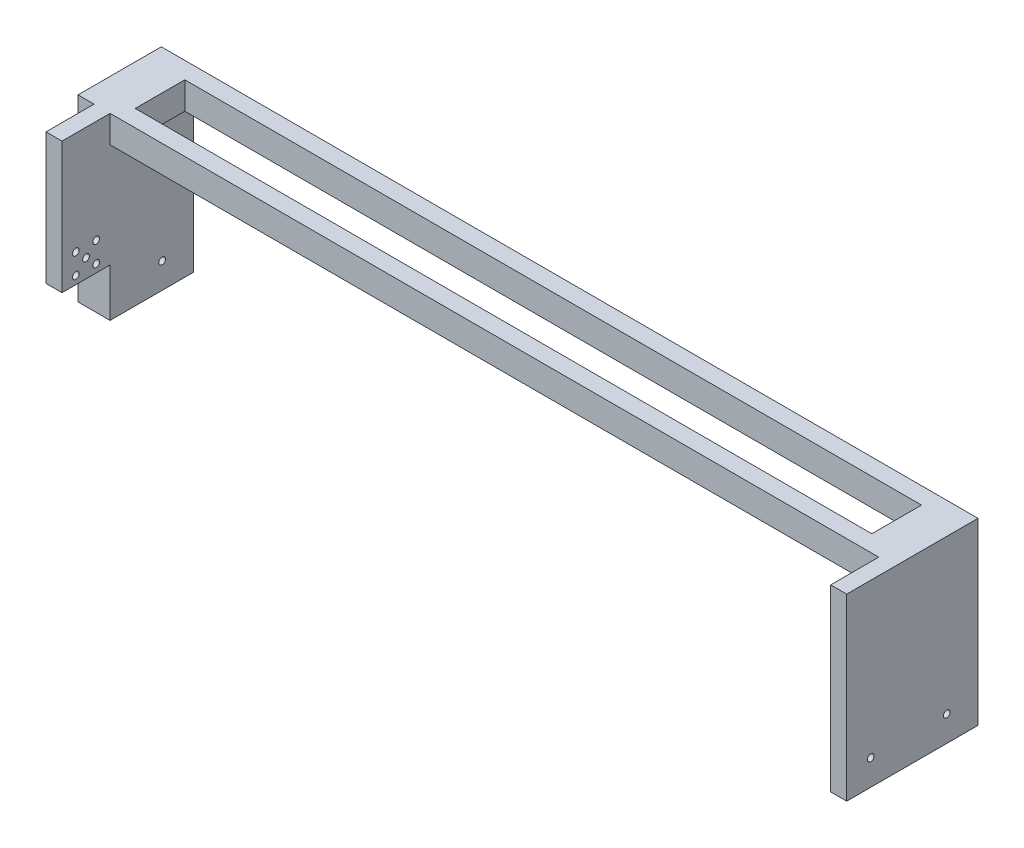
SolidWorks part; units mm, degrees
ref_plane "Front Plane" through (0, 0, 0) normal (0, 0, 1) x (1, 0, 0)
ref_plane "Top Plane" through (0, 0, 0) normal (0, 1, 0) x (1, 0, 0)
ref_plane "Right Plane" through (0, 0, 0) normal (1, 0, 0) x (0, 0, -1)
sketch "Sketch1" plane through (0, 0, 0) normal (0, 1, 0) x (1, 0, 0)
  line L0 (10, -82) -> (10, -52)
  line L1 (10, -52) -> (0, -52)
  line L2 (0, -52) -> (0, 0)
  line L4 (0, 0) -> (510, 0)
  line L5 (510, 0) -> (510, -82)
  line L8 (510, -82) -> (500, -82)
  line L9 (20, -82) -> (20, -52)
  line L10 (20, -52) -> (500, -52)
  line L11 (500, -52) -> (500, -82)
  line L12 (20, -82) -> (10, -82)
  dimension "D1" = 480
  dimension "D2" = 510
  dimension "D3" = 10
  dimension "D4" = 10
  dimension "D5" = 52
  dimension "D6" = 30
  dimension "D7" = 30
extrude "Boss-Extrude1" add sketch "Sketch1" along normal blind 82 and the other way blind 0.001 contours L9 L10 L11 L8 L5 L4 L2 L1 L0 L12
sketch "Sketch2" plane through (0, 0, 0) normal (0, 0, 1) x (1, 0, 0)
  line L0 (20, -0.001) -> (20, 64.999)
  line L1 (20, 82) -> (20, -0.001) construction
  line L2 (20, 64.999) -> (500, 64.999)
  line L3 (500, 82) -> (500, -0.001) construction
  line L4 (500, 64.999) -> (500, -0.001)
  line L5 (500, -0.001) -> (20, -0.001)
  dimension "D1" = 65
extrude "Cut-Extrude2" cut sketch "Sketch2" along normal blind 82
sketch "Sketch3" plane through (0, 0, 0) normal (0, 1, 0) x (1, 0, 0)
  line L0 (20, -82) -> (20, -52) construction
  line L1 (0, 0) -> (20, 0)
  line L2 (0, 0) -> (0, -52)
  line L3 (0, -52) -> (20, -52)
  line L4 (20, 0) -> (20, -52)
  line L5 (0, 0) -> (510, 0) construction
  line L6 (500, 0) -> (510, 0)
  line L7 (500, 0) -> (500, -82)
  line L8 (500, -82) -> (510, -82)
  line L9 (510, 0) -> (510, -82)
  line L10 (500, -52) -> (500, -82) construction
  line L11 (10, -52) -> (0, -52) construction
extrude "Boss-Extrude3" add sketch "Sketch3" against normal blind 30
sketch "Sketch4" plane through (510, 0, 0) normal (1, 0, 0) x (0, 0, -1)
  line L0 (-82, -30) -> (0, -30) construction
  line L2 (-82, -30) -> (-82, 82) construction
  circle A0 centre (-67, -14.051) radius 2.1
  circle A1 centre (-19.5, -14.05) radius 2.1
  dimension "D1" = 4.2
  dimension "D2" = 4.2
  dimension "D3" = 15.949
  dimension "D4" = 15
  dimension "D5" = 15.95
  dimension "D6" = 47.5
extrude "Cut-Extrude3" cut sketch "Sketch4" against normal blind 618
sketch "Sketch5" plane through (0, 82, 0) normal (0, 1, 0) x (1, 0, 0)
  line L0 (25.2, 0) -> (25.2, -52) construction
  line L1 (0, 0) -> (510, 0) construction
  line L2 (20, -82) -> (20, -52) construction
  line L3 (20, -52) -> (500, -52) construction
  line L4 (485.2, 0) -> (485.2, -52) construction
  line L6 (25.2, -10.5) -> (485.2, -10.5)
  line L7 (25.2, -10.5) -> (25.2, -41.5)
  line L8 (25.2, -41.5) -> (485.2, -41.5)
  line L9 (485.2, -41.5) -> (485.2, -10.5)
  line L10 (25.2, -203.3393) -> (25.2, 846.6607) construction
  dimension "D1" = 10.5
  dimension "D2" = 31
extrude "Cut-Extrude4" cut sketch "Sketch5" against normal blind 42
sketch "Sketch6" plane through (20, 0, 0) normal (1, 0, 0) x (0, 0, -1)
  line L0 (-82, -0.001) -> (-52, -0.001) construction
  line L3 (-67, -0.001) -> (-67, 29.5711) construction
  circle A0 centre (-67, 11.349) radius 2.1
  circle A1 centre (-60.65, 17.699) radius 2.1
  circle A2 centre (-73.35, 17.699) radius 2.1
  circle A3 centre (-73.35, 4.999) radius 2.1
  circle A4 centre (-60.65, 4.999) radius 2.1
  dimension "D5" = 4.2
  dimension "D6" = 12.7
  dimension "D1" = 12.7
  dimension "D2" = 6.35
  dimension "D3" = 12.7
  dimension "D4" = 6.35
  dimension "D7" = 6.35
  dimension "D8" = 6.35
  dimension "D9" = 6.35
  dimension "D10" = 5
  dimension "D11" = 29.5721
extrude "Cut-Extrude5" cut sketch "Sketch6" against normal blind 10
